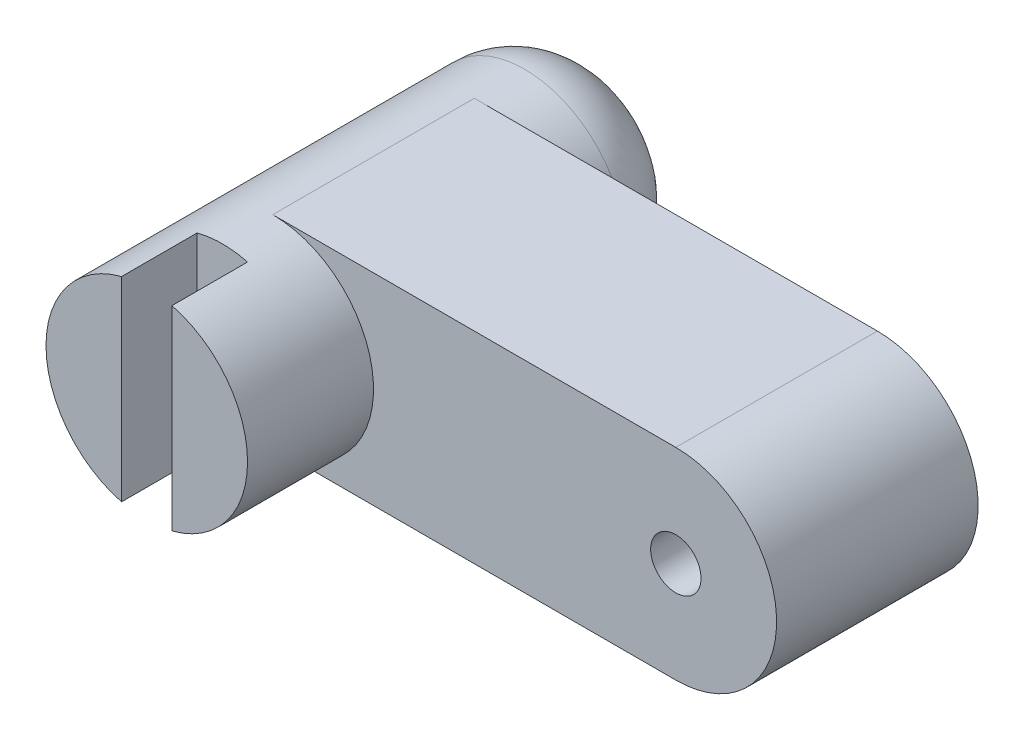
SolidWorks part; units mm, degrees
ref_plane "前视基准面" through (0, 0, 0) normal (0, 0, 1) x (1, 0, 0)
ref_plane "上视基准面" through (0, 0, 0) normal (0, 1, 0) x (1, 0, 0)
ref_plane "右视基准面" through (0, 0, 0) normal (1, 0, 0) x (0, 0, -1)
other "Configuration Table"
sketch "草图1" plane through (0, 0, 0) normal (0, 0, 1) x (1, 0, 0)
  circle A0 centre (0, 0) radius 2
  circle A1 centre (0, 0) radius 0.5
  dimension "D1" = 4
  dimension "D2" = 1
extrude "凸台-拉伸1" add sketch "草图1" along normal blind 9
sketch "草图2" plane through (0, 0, 9) normal (0, 0, 1) x (1, 0, 0)
  line L1 (-0.5, -2.0824) -> (0.5, -2.0824)
  line L2 (-0.5, -2.0824) -> (-0.5, 2.0824)
  line L3 (-0.5, 2.0824) -> (0.5, 2.0824)
  line L4 (0.5, -2.0824) -> (0.5, 2.0824)
  line L5 (-0.5, -2.0824) -> (0.5, 2.0824) construction
  line L6 (-0.5, 2.0824) -> (0.5, -2.0824) construction
  point P0 (0, 0)
  dimension "D1" = 1
extrude "切除-拉伸1" cut sketch "草图2" against normal blind 1.5
fillet "圆角2" radius 1.5 1 edges at (2, 0, 0)
sketch "草图3" plane through (0, 0, 0) normal (0, 1, 0) x (1, 0, 0)
  line L0 (0, 0) -> (0, -2.5) construction
  line L1 (0, -2.5) -> (0, -6.5)
  line L2 (0, -2.5) -> (8, -2.5)
  line L3 (8, -2.5) -> (8, -6.5)
  line L4 (0, -6.5) -> (8, -6.5)
  dimension "D1" = 2.5
  dimension "D2" = 4
  dimension "D3" = 8
  dimension "D4" = 4
extrude "凸台-拉伸2" add sketch "草图3" along normal mid plane 4
sketch "草图4" plane through (0, 0, 2.5) normal (0, 0, -1) x (-1, 0, 0)
  line L0 (-8, 2) -> (-8, -2) construction
  circle A0 centre (-8, 0) radius 2
  circle A1 centre (-8, 0) radius 0.5
  dimension "D1" = 1
extrude "凸台-拉伸3" add sketch "草图4" against normal blind 4
sketch "草图5" plane through (0, 0, 2.5) normal (0, 0, -1) x (-1, 0, 0)
  line L0 (-8, 0.5) -> (-8, -0.5) construction
  circle A0 centre (-8, 0) radius 0.5
  dimension "D1" = 1
extrude "切除-拉伸2" cut sketch "草图5" against normal blind 4
sketch "草图6" plane through (0, 0, 9) normal (0, 0, 1) x (1, 0, 0)
  circle A0 centre (0, 0) radius 0.5
  dimension "D1" = 1
extrude "切除-拉伸3" cut sketch "草图6" against normal through all
